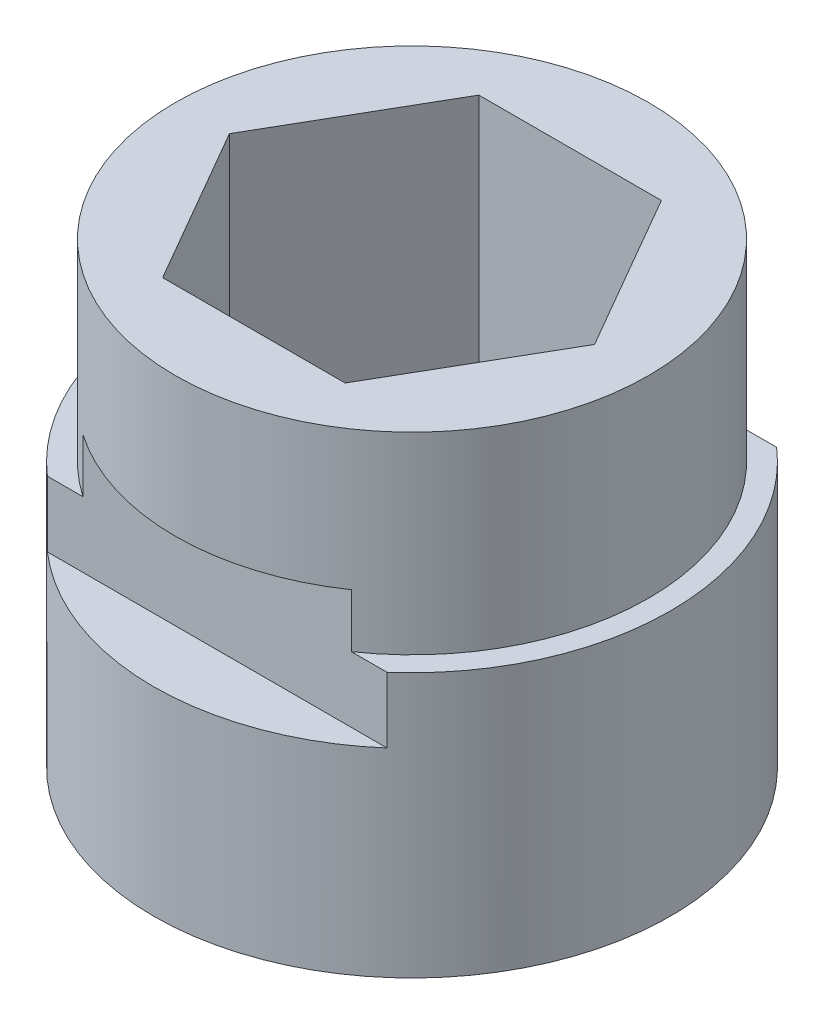
SolidWorks part; units mm, degrees
material "Polyester Resin"
ref_plane "Front Plane" through (0, 0, 0) normal (0, 0, 1) x (1, 0, 0)
ref_plane "Top Plane" through (0, 0, 0) normal (0, 1, 0) x (1, 0, 0)
ref_plane "Right Plane" through (0, 0, 0) normal (1, 0, 0) x (0, 0, -1)
sketch "Sketch1" plane through (0, 0, 0) normal (0, 1, 0) x (1, 0, 0)
  line L1 (-2.9156, 5.05) -> (-5.8312, 0)
  line L2 (-5.8312, 0) -> (-2.9156, -5.05)
  line L3 (-2.9156, -5.05) -> (2.9156, -5.05)
  line L4 (2.9156, -5.05) -> (5.8312, 0)
  line L5 (5.8312, 0) -> (2.9156, 5.05)
  line L6 (2.9156, 5.05) -> (-2.9156, 5.05)
  circle A0 centre (0, 0) radius 5.05 construction
  circle A1 centre (0, 0) radius 7.5565
  dimension "D2" = 15.113
  dimension "D1" = 10.1
extrude "Boss-Extrude1" add sketch "Sketch1" along normal blind 13.97
sketch "Sketch2" plane through (0, 0, 0) normal (0, -1, 0) x (1, 0, 0)
  circle A0 centre (0, 0) radius 7.5565
  circle A1 centre (0, 0) radius 3.3
  dimension "D1" = 6.6
extrude "Boss-Extrude2" add sketch "Sketch2" along normal blind 0.635
sketch "Sketch4" plane through (0, -0.635, 0) normal (0, -1, 0) x (1, 0, 0)
  circle A0 centre (0, 0) radius 7.5565
  circle A1 centre (0, 0) radius 8.255
  dimension "D1" = 16.51
extrude "Boss-Extrude3" add sketch "Sketch4" against normal blind 8.4455
sketch "Sketch3" plane through (0, 0, 0) normal (1, 0, 0) x (0, 0, -1)
  line L0 (-6.223, 9.525) -> (-6.223, 5.715)
  line L1 (6.223, 9.525) -> (6.223, 5.715)
  line L2 (-7.5565, -0.635) -> (7.5565, -0.635) construction
  line L3 (-6.223, 9.525) -> (-8.7958, 9.525)
  line L4 (-8.7958, 9.525) -> (-8.7958, 5.715)
  line L5 (-8.7958, 5.715) -> (-6.223, 5.715)
  line L6 (6.223, 9.525) -> (8.4791, 9.525)
  line L7 (8.4791, 9.525) -> (8.4791, 5.715)
  line L8 (8.4791, 5.715) -> (6.223, 5.715)
  dimension "D1" = 12.446
  dimension "D2" = 6.223
  dimension "D3" = 3.81
  dimension "D4" = 3.81
  dimension "D5" = 6.35
  dimension "D6" = 6.35
extrude "Cut-Extrude1" cut sketch "Sketch3" against normal through all and the other way through all
equation "\"AB_Central_Bushing_Length\"= .4724in"
equation "\"Solid_Length\"= .025in"
equation "\"Hex_Length\"=0.55"
equation "\"D1@Boss-Extrude1\"= \"Hex_Length\""
equation "\"D1@Boss-Extrude2\"=\"Solid_Length\""
equation "\"Cutout_Angle\"= 80"
